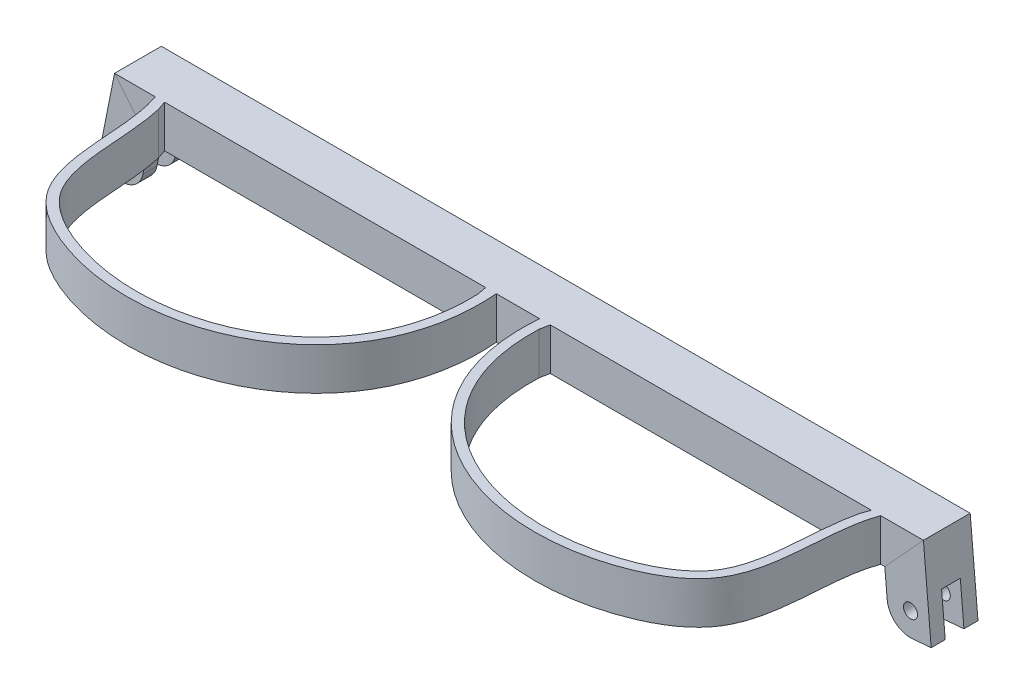
SolidWorks part; units mm, degrees
ref_plane "前视基准面" through (0, 0, 0) normal (0, 0, 1) x (1, 0, 0)
ref_plane "上视基准面" through (0, 0, 0) normal (0, 1, 0) x (1, 0, 0)
ref_plane "右视基准面" through (0, 0, 0) normal (1, 0, 0) x (0, 0, -1)
sketch "草图1" plane through (0, 0, 0) normal (0, 1, 0) x (1, 0, 0)
  line L0 (-85, 29.8187) -> (85, 29.8187)
  line L1 (85, 29.8187) -> (85, -30.1813)
  line L2 (85, -30.1813) -> (-85, -30.1813)
  line L3 (-85, -30.1813) -> (-85, 29.8187)
  line L4 (-77.5, 21.6616) -> (77.5, 21.6616)
  line L5 (-77.5, 21.6616) -> (-77.5, 11.6616)
  line L6 (-77.5, 11.6616) -> (-4.6224, 11.6616)
  line L8 (-74.8263, 9.6616) -> (-6.5113, 9.6616) construction
  line L10 (-4.6224, 11.6616) -> (4.6224, 11.6616)
  line L11 (0, 29.8187) -> (0, -30.1813) construction
  line L12 (77.5, 11.6616) -> (4.6224, 11.6616)
  line L13 (77.5, 21.6616) -> (77.5, 11.6616)
  spline S0 degree 3 poles (-77.5, 11.6616) (-74.4077, 3.1869) (-78.1308, -15.9273) (-40.2589, -37.426) (-2.1163, -20.689) (-4.6224, 11.6616) knots 0 0 0 0 0.246122 0.369792 1 1 1 1
  spline S1 degree 1 poles (-74.8263, 9.6616) (-6.5113, 9.6616) knots 0 0 1 1 construction
  spline S2 degree 3 poles (-74.8263, 9.6616) (-74.5371, 8.4402) (-74.1186, 5.9785) (-73.6218, 0.8691) (-73.2546, -5.557) (-72.241, -11.3706) (-70.6014, -15.2078) (-68.2701, -18.4305) (-63.7315, -21.7629) (-56.8543, -24.5334) (-49.7226, -26.1197) (-40.0582, -26.6566) (-30.6361, -24.878) (-22.3142, -20.9083) (-16.8289, -16.8747) (-12.2912, -11.8166) (-9.4499, -6.76) (-7.8343, -2.2025) (-6.9771, 1.4731) (-6.5812, 4.7599) (-6.4697, 7.5102) (-6.4856, 8.9503) (-6.5113, 9.6616) knots 0.022831 0.022831 0.022831 0.022831 0.052972 0.083113 0.143395 0.203676 0.233817 0.263958 0.324239 0.384521 0.444802 0.505084 0.625647 0.685929 0.74621 0.806492 0.866773 0.896914 0.927055 0.957196 0.972266 0.987337 0.987337 0.987337 0.987337
  spline S3 degree 1 poles (-74.8263, 9.6616) (-75.4985, 11.6616) knots 0 0 1 1
  spline S4 degree 1 poles (-6.5113, 9.6616) (-6.9074, 11.6616) knots 0 0 1 1
  spline S5 degree 1 poles (74.8263, 9.6616) (75.4985, 11.6616) knots 0 0 1 1
  spline S6 degree 1 poles (6.5113, 9.6616) (6.9074, 11.6616) knots 0 0 1 1
  spline S7 degree 3 poles (74.8263, 9.6616) (74.5371, 8.4402) (74.1186, 5.9785) (73.6218, 0.8691) (73.2546, -5.557) (72.241, -11.3706) (70.6014, -15.2078) (68.2701, -18.4305) (63.7315, -21.7629) (56.8543, -24.5334) (49.7226, -26.1197) (40.0582, -26.6566) (30.6361, -24.878) (22.3142, -20.9083) (16.8289, -16.8747) (12.2912, -11.8166) (9.4499, -6.76) (7.8343, -2.2025) (6.9771, 1.4731) (6.5812, 4.7599) (6.4697, 7.5102) (6.4856, 8.9503) (6.5113, 9.6616) knots 0.022831 0.022831 0.022831 0.022831 0.052972 0.083113 0.143395 0.203676 0.233817 0.263958 0.324239 0.384521 0.444802 0.505084 0.625647 0.685929 0.74621 0.806492 0.866773 0.896914 0.927055 0.957196 0.972266 0.987337 0.987337 0.987337 0.987337
  spline S8 degree 3 poles (77.5, 11.6616) (74.4077, 3.1869) (78.1308, -15.9273) (40.2589, -37.426) (2.1163, -20.689) (4.6224, 11.6616) knots 0 0 0 0 0.246122 0.369792 1 1 1 1
  point P3 (0, 29.8187)
  point P25 (0, 11.6616)
  point P31 (0, 21.6616)
  dimension "D1" = 60
  dimension "D2" = 170
  dimension "D3" = 10
  dimension "D4" = 77.5
  dimension "D5" = 2
extrude "frame_前端" add sketch "草图1" along normal blind 9 contours L13 L4 L5 L6 L10 L12 | S8 L12 S5 S7 S6 | S4 S2 S3 L6 S0 region at (0, 0, -16.6616) region at (-76.4992, 0, -10.8291) region at (42.3457, 0, 27.4934)
sketch "左镜腿扫描截面草图" plane through (77.5, 0, 0) normal (1, 0, 0) x (0, 0, -1)
  line L0 (11.6616, 9) -> (11.6616, 0)
  line L1 (11.6616, 9) -> (11.6616, 0) construction
  line L2 (11.6616, 0) -> (21.6616, 0)
  line L3 (21.6616, 0) -> (21.6616, 9)
  line L4 (21.6616, 9) -> (11.6616, 9)
  line L5 (11.6616, 9) -> (21.6616, 0) construction
  line L6 (11.6616, 0) -> (21.6616, 9) construction
  point P7 (16.6616, 4.5)
ref_plane "左侧镜腿轨迹基准面" through (0, 0, -16.6616) normal (0, 0, -1) x (-1, 0, 0)
sketch "左侧镜腿轨迹草图" plane through (0, 0, -16.6616) normal (0, 0, -1) x (-1, 0, 0)
  line L0 (-77.5, 4.5) -> (-82.5, 4.5)
  line L1 (-77.5, 0) -> (-77.5, 9) construction
  line L2 (-82.5, 4.5) -> (-83.8073, -10.4429)
  dimension "D1" = 5
  dimension "D2" = 15
  dimension "D3" = 95
sweep "左侧connection生成" add profiles "左镜腿扫描截面草图" path "左侧镜腿轨迹草图"
sketch "草图20" plane through (0, 0, -21.6616) normal (0, 0, -1) x (-1, 0, 0)
  line L8 (-79.3245, -10.8351) -> (-84.3054, -10.3993)
  line L9 (-79.3245, -10.8351) -> (-88.2902, -10.0507) construction
  line L10 (-78.3765, 0) -> (-79.3245, -10.8351) construction
  line L11 (-78.8887, -5.8541) -> (-79.3245, -10.8351)
  arc A1 (-84.3054, -10.3993) -> (-78.8887, -5.8541) centre (-83.8697, -5.4184) ccw
  point P13 (-79.3245, -10.8351)
  dimension "D1" = 5
extrude "左侧connection圆角化" cut sketch "草图20" against normal through all
sketch "孔左" plane through (0, 0, -21.6616) normal (0, 0, -1) x (-1, 0, 0)
  line L4 (-78.8887, -5.8541) -> (-78.3765, 0)
  line L5 (-78.3765, 0) -> (-86.6235, 9)
  line L6 (-86.6235, 9) -> (-88.2902, -10.0507)
  line L7 (-88.2902, -10.0507) -> (-84.3054, -10.3993)
  line L8 (-78.8887, -5.8541) -> (-78.3765, 0)
  line L9 (-78.3765, 0) -> (-86.6235, 9)
  line L10 (-86.6235, 9) -> (-88.2902, -10.0507)
  line L11 (-88.2902, -10.0507) -> (-84.3054, -10.3993)
  arc A1 (-84.3054, -10.3993) -> (-78.8887, -5.8541) centre (-83.8697, -5.4184) ccw
  circle A3 centre (-83.8697, -5.4184) radius 1.5
  arc A4 (-84.3054, -10.3993) -> (-78.8887, -5.8541) centre (-83.8697, -5.4184) ccw
  dimension "D2" = 3
  dimension "D1" = 0
ref_plane "右侧镜腿轨迹基准面" through (0, 0, -16.6616) normal (0, 0, -1) x (-1, 0, 0)
sketch "草图22" plane through (0, 0, -16.6616) normal (0, 0, -1) x (-1, 0, 0)
  line L0 (77.5, 4.5) -> (82.5, 4.5)
  line L1 (77.5, 9) -> (77.5, 0) construction
  line L2 (82.5, 4.5) -> (85.4316, -10.2107)
  dimension "D1" = 5
  dimension "D2" = 15
sketch "草图23" plane through (-77.5, 0, 0) normal (-1, 0, 0) x (0, 0, 1)
  line L2 (-21.6616, 0) -> (-11.6616, 0)
  line L3 (-11.6616, 0) -> (-11.6616, 9)
  line L6 (-21.6616, 9) -> (-21.6616, 0)
  line L7 (-21.6616, 0) -> (-21.6616, 9) construction
  line L8 (-21.6616, 9) -> (-11.6616, 9) construction
  line L9 (-21.6616, 9) -> (-11.6616, 9)
sweep "右侧connection生成" add profiles "草图23" path "草图22"
sketch "草图24" plane through (0, 0, -21.6616) normal (0, 0, -1) x (-1, 0, 0)
  line L2 (89.8449, -9.3312) -> (81.0184, -11.0902) construction
  line L3 (81.0184, -11.0902) -> (85.4316, -10.2107)
  line L4 (81.0184, -11.0902) -> (80.1389, -6.677)
  line L5 (78.8083, 0) -> (81.0184, -11.0902) construction
  circle A1 centre (84.972, -5.204) radius 1.5
  arc A2 (80.1389, -6.677) -> (85.4316, -10.2107) centre (84.5521, -5.7975) ccw
  dimension "D3" = 3
  dimension "D1" = 4.5
extrude "右侧孔and_connection圆角化" cut sketch "草图24" against normal through all
ref_plane "线槽口草图基准面" through (0, 0, 0) normal (1, 0, 0) x (0, 0, -1)
sketch "草图25" plane through (0, 0, 0) normal (1, 0, 0) x (0, 0, -1)
  line L6 (21.6616, 9) -> (21.6616, -10.0507) construction
  line L9 (11.6616, 9) -> (21.6616, 0) construction
  line L10 (11.6616, 0) -> (21.6616, 9) construction
  line L11 (13.6616, 0) -> (13.6616, 7.2)
  line L12 (13.6616, 7.2) -> (19.6616, 7.2)
  line L13 (19.6616, 7.2) -> (19.6616, 0)
  line L14 (13.6616, 0) -> (19.6616, 0)
  dimension "D1" = 2
  dimension "D2" = 2
extrude "挖槽右" cut sketch "草图25" against normal blind 77.5
extrude "挖槽左" cut sketch "草图25<2>" along normal blind 77.5
sketch "草图25<2>" plane through (0, 0, 0) normal (1, 0, 0) x (0, 0, -1) same geometry as "草图25"
sketch "草图26" plane through (0, 0, -21.6616) normal (0, 0, -1) x (-1, 0, 0)
  line L6 (-88.2902, -10.0507) -> (-87.5058, -1.085)
  line L7 (-86.6235, 9) -> (-88.2902, -10.0507) construction
  line L8 (-87.5058, -1.085) -> (-78.5401, -1.8694)
  line L9 (-78.8887, -5.8541) -> (-78.3765, 0) construction
  line L10 (-78.5401, -1.8694) -> (-78.9323, -6.3522)
  line L11 (-88.2902, -10.0507) -> (-83.8073, -10.4429)
  line L12 (-88.2902, -10.0507) -> (-84.3054, -10.3993) construction
  arc A1 (-83.8073, -10.4429) -> (-78.9323, -6.3522) centre (-83.4151, -5.96) ccw
  dimension "D2" = 4.5
  dimension "D1" = 9
  dimension "D3" = 4.5
extrude "挖孔左" cut sketch "孔左" against normal through all contours A3
ref_plane "基准面1" through (0, 0, -16.6616) normal (0, 0, -1) x (-1, 0, 0)
sketch "草图27" plane through (0, 0, -16.6616) normal (0, 0, -1) x (-1, 0, 0)
  line L0 (-87.5058, -1.085) -> (-78.5401, -1.8694)
  line L1 (-78.5401, -1.8694) -> (-78.9323, -6.3522)
  line L2 (-87.5058, -1.085) -> (-88.2902, -10.0507)
  line L3 (-88.2902, -10.0507) -> (-83.8073, -10.4429)
  arc A0 (-83.8073, -10.4429) -> (-78.9323, -6.3522) centre (-83.4151, -5.96) ccw
extrude "左侧connection口" cut sketch "草图27" against normal blind 2 and the other way blind 2
ref_plane "基准面2" through (0, 0, -16.6616) normal (0, 0, -1) x (-1, 0, 0)
sketch "草图30" plane through (0, 0, -16.6616) normal (0, 0, -1) x (-1, 0, 0)
  line L0 (89.8449, -9.3312) -> (85.4316, -10.2107)
  line L1 (89.8449, -9.3312) -> (88.0861, -0.5059)
  line L2 (86.1917, 9) -> (89.8449, -9.3312) construction
  line L3 (88.0861, -0.5059) -> (79.2597, -2.2649)
  line L4 (78.8083, 0) -> (80.1389, -6.677) construction
  line L5 (79.2597, -2.2649) -> (80.1389, -6.677)
  arc A0 (80.1389, -6.677) -> (85.4316, -10.2107) centre (84.5521, -5.7975) ccw
extrude "切除-拉伸3" cut sketch "草图30" against normal blind 2 and the other way blind 2
